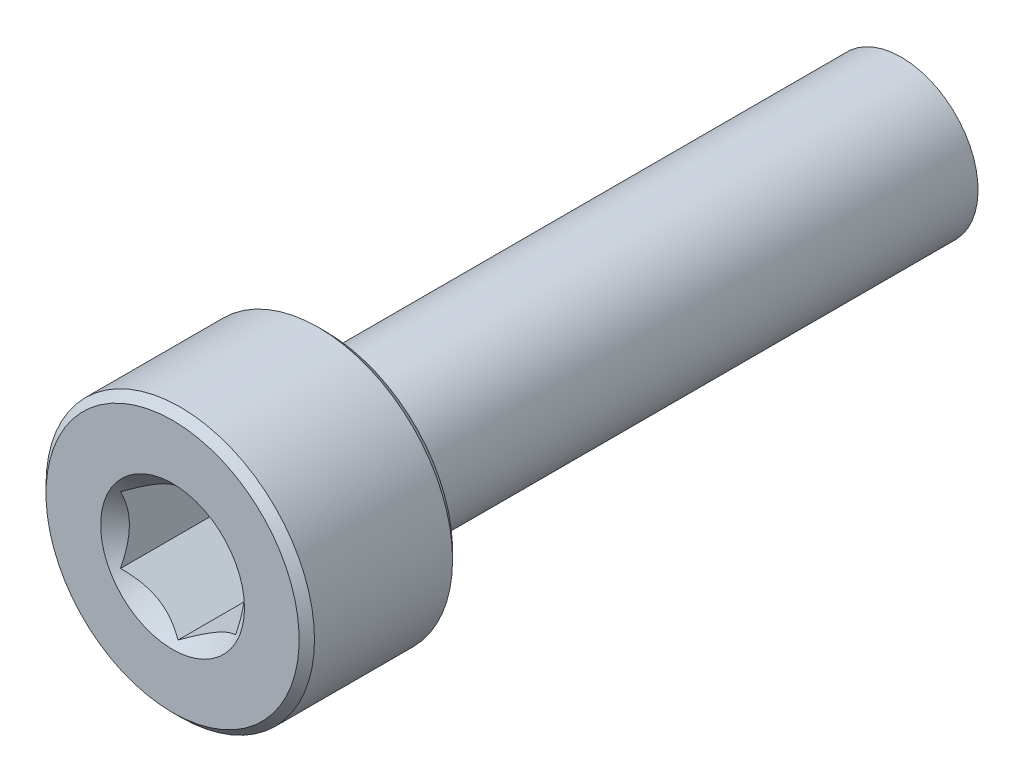
SolidWorks part; units mm, degrees
ref_plane "Front Plane" through (0, 0, 0) normal (0, 0, 1) x (1, 0, 0)
ref_plane "Top Plane" through (0, 0, 0) normal (0, 1, 0) x (1, 0, 0)
ref_plane "Right Plane" through (0, 0, 0) normal (1, 0, 0) x (0, 0, -1)
sketch "Sketch1" plane through (0, 0, 0) normal (1, 0, 0) x (0, 0, -1)
  line L0 (-7, 0) -> (7, 0) construction
  line L1 (7, 0) -> (7, 1.5453) construction
  line L2 (7, 1.5453) -> (6.5453, 2) construction
  line L3 (6.5453, 2) -> (6.475, 2) construction
  line L4 (6.475, 2) -> (-3, 2) construction
  line L5 (-3, 2) -> (-3, 3.5) construction
  line L6 (-3, 3.5) -> (-7, 3.5) construction
  line L7 (-7, 3.5) -> (-7, 0) construction
  line L8 (7, 1.5453) -> (7, 2) construction
  line L9 (6.9562, 2.0758) -> (7.3062, 1.4696) construction
  line L10 (7.3062, 1.4696) -> (7.6562, 2.0758) construction
  line L11 (7.6562, 2.0758) -> (6.9562, 2.0758) construction
  line L12 (7.3062, 2.0758) -> (7.3062, 2) construction
  line L13 (7.3062, 1.4696) -> (7.3062, 1.5453) construction
  line L14 (7.2625, 1.5453) -> (7.35, 1.5453) construction
  line L15 (7, 2) -> (7.6125, 2) construction
  line L16 (6.9781, 2.0379) -> (7.6344, 2.0379) construction
  line L17 (7, 0) -> (7, -2) construction
  line L18 (-3.2, 3.5) -> (-3, 3.3) construction
  line L19 (-6.8, 3.5) -> (-7, 3.3) construction
  line L20 (-3, 2) -> (-3, 0) construction
  line L21 (-3, 1) -> (0.3333, 1) construction
  line L22 (0.3333, 1) -> (3.6667, 1) construction
  line L23 (3.6667, 1) -> (7, 1) construction
  line L24 (0.3333, 1) -> (0.3333, 2) construction
  line L25 (0.3333, 2) -> (0.3333, 3.5) construction
  line L26 (3.6667, 1) -> (3.6667, 3.5) construction
  point P0 (-7, 1.5)
  point P3 (5.25, 2)
  point P4 (0, 0)
  point P18 (3.6667, 2)
  point P22 (7.3062, 1.5453)
  point P24 (6.475, 2)
  point P25 (7.3062, 2)
  point P28 (7.3062, 2.0379)
  point P29 (5.25, -2)
  point P30 (0.3333, 2)
  point P31 (-5, 3.5)
  point P37 (-3.7, 3.5)
  point P38 (-6.7, 3.5)
  point P45 (0.3333, 1)
  point P46 (3.6667, 1)
  dimension "D2" = 0.0875
  dimension "D7" = 0.2
  dimension "D8" = 0.2
  dimension "D9" = 0.2
  dimension "D10" = 0.1
  dimension "D11" = 0.5
  dimension "Drive Size" = 3
  dimension "Head Diameter" = 7
  dimension "Head Height" = 4
  dimension "Thread Pitch" = 0.7
  dimension "Thread Size" = 4
  dimension "Length" = 10
  dimension "D12" = 0.525
  dimension "D4" = 1.75
  dimension "D3" = 45
sketch "Sketch2" plane through (0, 0, 0) normal (1, 0, 0) x (0, 0, -1)
  line L0 (-7, 0) -> (-7, 3.3)
  line L1 (-6.8, 3.5) -> (-3.2, 3.5)
  line L2 (-3, 3.3) -> (-3, 2.2)
  line L4 (6.5453, 2) -> (7, 1.5453)
  line L5 (7, 1.5453) -> (7, 0)
  line L6 (-3, 3.5) -> (-7, 3.5) construction
  line L7 (7, 0) -> (-7, 0)
  line L8 (-6.8, 3.5) -> (-7, 3.3) construction
  line L10 (-6.8, 3.5) -> (-7, 3.3)
  line L14 (-3.2, 3.5) -> (-3, 3.3) construction
  line L16 (-3.2, 3.5) -> (-3, 3.3)
  line L17 (-3, 2) -> (-3, 3.5) construction
  line L19 (-2.8, 2) -> (6.5453, 2)
  line L20 (6.475, 2) -> (-3, 2) construction
  arc A1 (-3, 2.2) -> (-2.8, 2) centre (-2.8, 2.2) ccw
  dimension "D3" = 0.2
revolve "Revolve1" add sketch "Sketch2" angle 360 about L7
sketch "Sketch3" plane through (0, 0, 7) normal (0, 0, 1) x (1, 0, 0)
  line L1 (1.5, -0.866) -> (1.5, 0.866)
  line L2 (1.5, 0.866) -> (0, 1.7321)
  line L3 (0, 1.7321) -> (-1.5, 0.866)
  line L4 (-1.5, 0.866) -> (-1.5, -0.866)
  line L5 (-1.5, -0.866) -> (0, -1.7321)
  line L6 (0, -1.7321) -> (1.5, -0.866)
  circle A0 centre (0, 0) radius 1.5 construction
  circle A1 centre (0, 0) radius 3.5 construction
  circle A2 centre (0, 0) radius 3.5 construction
  circle A3 centre (0, 0) radius 1.7321 construction
  point P13 (0, 0)
extrude "Cut-Extrude1" cut sketch "Sketch3" against normal offset from surface (3 mm away) 1 up to face at (0, 3.3, 3)
sketch "Sketch4" plane through (0, 0, 7) normal (0, 0, 1) x (1, 0, 0)
  circle A0 centre (0, 0) radius 1.875
  dimension "D1" = 3.75
extrude "Cut-Extrude2" cut sketch "Sketch4" against normal up to vertex (2 mm away) draft 45 up to point (0, 3.5, 5)
sketch "Sketch11" plane through (0, 0, 0) normal (1, 0, 0) x (0, 0, -1)
  line L0 (-7, 0) -> (7, 0) construction
  line L1 (-7, 0) -> (7, 0) construction
  line L2 (-1.125, 0) -> (-1.125, 2) construction
  line L3 (6.475, 2) -> (-3, 2) construction
  line L4 (5.125, 0) -> (5.125, 2) construction
  line L6 (7, 1.5453) -> (7, 2) construction
  point P2 (-1.125, 0)
  point P3 (5.125, 0)
  dimension "D1" = 1.875
  dimension "D2" = 1.875
sketch "Sketch8" [suppressed] plane through (0, 0, 0) normal (1, 0, 0) x (0, 0, -1)
  line L0 (-3, 0) -> (-3, 2)
  line L1 (-2.8, -2) -> (-2.8, 2) construction
  line L2 (-3, 2) -> (-2.8, 2)
  line L4 (-2.8, 2) -> (-1.6453, 0)
  line L5 (-1.6453, 0) -> (-3, 0)
  line L6 (6.475, 2) -> (-3, 2) construction
  line L7 (-7, 0) -> (7, 0) construction
  dimension "D1" = 60
sketch "Sketch12" plane through (0, 0, 3) normal (0, 0, -1) x (-1, 0, 0)
  circle A0 centre (0, 0) radius 2 construction
  circle A1 centre (0, 0) radius 2
extrude "Boss-Extrude1" add sketch "Sketch12" along normal blind 15
equation "\"D2@Sketch1\" = \"Thread Pitch@Sketch1\" / 8"
equation "\"D7@Sketch1\" = \"Head Height@Sketch1\" * .05"
equation "\"D8@Sketch1\"=\"D7@Sketch1\""
equation "\"D9@Sketch1\"=\"D7@Sketch1\""
equation "\"D10@Sketch1\"=\"D7@Sketch1\"/2"
equation "\"D11@Sketch1\"=\"D10@Sketch1\"*5"
equation "\"D4@Sketch1\"=\"Thread Pitch@Sketch1\"*2.5"
equation "\"D12@Sketch1\"=\"Thread Pitch@Sketch1\"*.75"
equation "\"D3@Sketch2\" = \"Thread Size@Sketch1\" * 0.05"
equation "\"D1@Sketch11\"=\"Length@Sketch1\"*0.1875"
equation "\"D2@Sketch11\"=\"D1@Sketch11\""
equation "\"D1@Sketch4\"=\"Drive Size@Sketch1\"*1.25"
